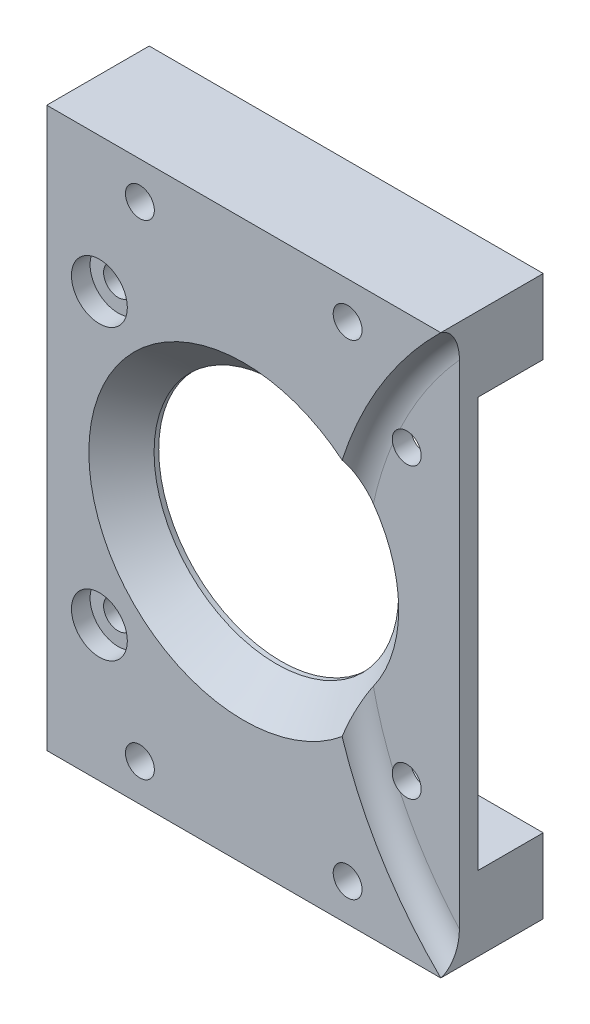
SolidWorks part; units mm, degrees
ref_plane "Front Plane" through (0, 0, 0) normal (0, 0, 1) x (1, 0, 0)
ref_plane "Top Plane" through (0, 0, 0) normal (0, 1, 0) x (1, 0, 0)
ref_plane "Right Plane" through (0, 0, 0) normal (1, 0, 0) x (0, 0, -1)
sketch "Sketch1" plane through (0, 0, 0) normal (0, 0, 1) x (1, 0, 0)
  line L0 (21.15, -17.4429) -> (21.15, 17.4429) construction
  line L1 (21.15, -30) -> (-21.15, -30)
  line L2 (21.15, -30) -> (21.15, 30)
  line L3 (21.15, 30) -> (-21.15, 30)
  line L4 (-21.15, -30) -> (-21.15, 30)
  line L7 (-21.15, 17.4429) -> (-21.15, -17.4429) construction
  line L8 (17.4429, -20.65) -> (20.65, -17.4429)
  line L9 (20.65, -17.4429) -> (20.65, 17.4429)
  line L10 (20.65, 17.4429) -> (17.4429, 20.65)
  line L11 (17.4429, 20.65) -> (-17.4429, 20.65)
  line L12 (-17.4429, 20.65) -> (-20.65, 17.4429)
  line L13 (-20.65, 17.4429) -> (-20.65, -17.4429)
  line L14 (-20.65, -17.4429) -> (-17.4429, -20.65)
  line L15 (-17.4429, -20.65) -> (17.4429, -20.65)
  line L16 (17.4429, -20.65) -> (20.65, -17.4429) construction
  line L17 (20.65, -17.4429) -> (20.65, 17.4429) construction
  line L18 (20.65, 17.4429) -> (17.4429, 20.65) construction
  line L19 (17.4429, 20.65) -> (-17.4429, 20.65) construction
  line L20 (-17.4429, 20.65) -> (-20.65, 17.4429) construction
  line L21 (-20.65, 17.4429) -> (-20.65, -17.4429) construction
  line L22 (-20.65, -17.4429) -> (-17.4429, -20.65) construction
  line L23 (-17.4429, -20.65) -> (17.4429, -20.65) construction
  line L24 (21.15, 0) -> (-21.15, 0) construction
  circle A0 centre (0, 0) radius 13.1303 construction
  circle A1 centre (0, 0) radius 13.1303
  circle A2 centre (-15.5, 15.5) radius 1.55
  arc A3 (-15.5, 13.9649) -> (-15.9358, 16.972) centre (-15.5, 15.5) ccw construction
  circle A4 centre (15.5, 15.5) radius 1.55
  circle A5 centre (15.5, -15.5) radius 1.55
  circle A6 centre (-15.5, -15.5) radius 1.55
  point P21 (0, 0)
  dimension "D2" = 3.1
  dimension "D3" = 4
  dimension "D4" = 60
  dimension "D1" = 0
extrude "Boss-Extrude1" add sketch "Sketch1" along normal blind 4
chamfer "Chamfer1" distance 3.5 angle 45 1 edges at (13.1303, 0, 4)
sketch "Sketch8" plane through (0, 0, 4) normal (0, 0, 1) x (1, 0, 0)
  line L1 (21.15, -30) -> (21.15, 30)
  line L2 (21.15, 30) -> (-21.15, 30) construction
  line L3 (21.15, -30) -> (21.15, 30) construction
  arc A2 (21.15, -30) -> (21.15, 30) centre (50.5439, 0) cw
  dimension "D1" = 42
extrude "Cut-Extrude2" cut sketch "Sketch8" against normal blind 2
sketch "Sketch9" plane through (0, 0, 4) normal (0, 0, 1) x (1, 0, 0)
  circle A0 centre (-15.5, -15.5) radius 3
  circle A3 centre (-15.5, -15.5) radius 1.55 construction
  circle A4 centre (-15.5, 15.5) radius 3
  circle A5 centre (-15.5, 15.5) radius 1.55 construction
  dimension "D1" = 6
  dimension "D2" = 6
extrude "Cut-Extrude3" cut sketch "Sketch9" against normal up to surface (2 mm away) up to face at (13.95, 15.5, 2)
fillet "Fillet6" radius 2.5 2 edges at (14.2434, 21.1251, 2) (14.2434, -21.1251, 2)
sketch "Sketch10" plane through (0, 0, 0) normal (0, 0, -1) x (-1, 0, 0)
  line L0 (-21.15, -30) -> (-21.15, 30) construction
  line L1 (21.15, -30) -> (-21.15, -30)
  line L2 (21.15, -30) -> (21.15, -22)
  line L3 (21.15, -22) -> (-21.15, -22)
  line L4 (-21.15, -30) -> (-21.15, -22)
  line L5 (21.15, -26) -> (-21.15, -26) construction
  line L6 (21.15, 30) -> (-21.15, 30)
  line L7 (21.15, 30) -> (21.15, 22)
  line L8 (21.15, 22) -> (-21.15, 22)
  line L9 (-21.15, 30) -> (-21.15, 22)
  line L10 (0, -30) -> (0, -22) construction
  line L11 (0, 0) -> (21.15, 0) construction
  line L12 (21.15, 30) -> (21.15, -30) construction
  circle A0 centre (11.15, -26) radius 1.55
  circle A1 centre (-11.15, -26) radius 1.55
  circle A2 centre (-11.15, 26) radius 1.55
  circle A3 centre (11.15, 26) radius 1.55
  dimension "D3" = 10
  dimension "D4" = 3.1
  dimension "D1" = 8
  dimension "D2" = 8
extrude "Boss-Extrude2" add sketch "Sketch10" along normal blind 7
sketch "Sketch11" plane through (0, 0, 0) normal (0, 0, -1) x (-1, 0, 0)
  circle A0 centre (-11.15, 26) radius 1.55 construction
  circle A1 centre (11.15, 26) radius 1.55 construction
  circle A2 centre (-11.15, -26) radius 1.55 construction
  circle A3 centre (11.15, -26) radius 1.55 construction
  circle A4 centre (-11.15, 26) radius 1.55
  circle A5 centre (11.15, 26) radius 1.55
  circle A6 centre (-11.15, -26) radius 1.55
  circle A7 centre (11.15, -26) radius 1.55
extrude "Cut-Extrude4" cut sketch "Sketch11" against normal up to surface (4 mm away) up to face at (-12.5, -15.5, 4)
